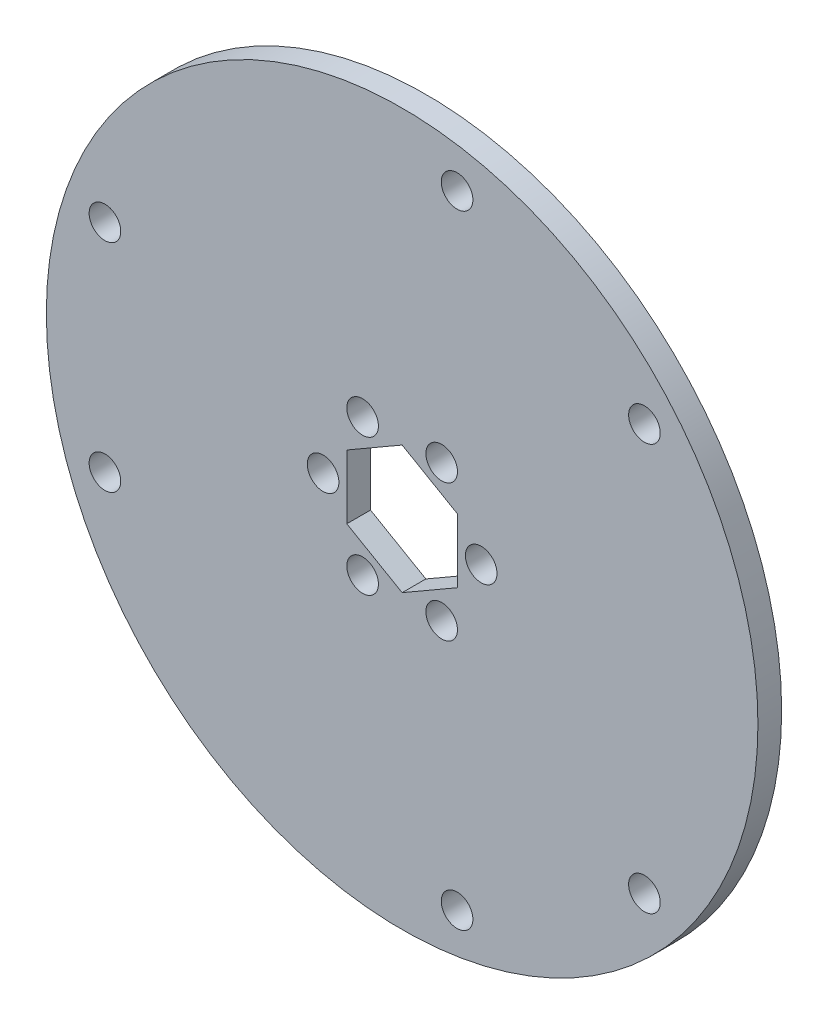
SolidWorks part; units mm, degrees
material "ABS PC"
ref_plane "Front Plane" through (0, 0, 0) normal (0, 0, 1) x (1, 0, 0)
ref_plane "Top Plane" through (0, 0, 0) normal (0, 1, 0) x (1, 0, 0)
ref_plane "Right Plane" through (0, 0, 0) normal (1, 0, 0) x (0, 0, -1)
sketch "Sketch1" plane through (0, 0, 0) normal (0, 0, 1) x (1, 0, 0)
  line L0 (0, 8.0829) -> (7, 4.0415)
  line L1 (-7, -4.0415) -> (-7, 4.0415)
  line L2 (0, -8.0829) -> (-7, -4.0415)
  line L3 (-7, 4.0415) -> (0, 8.0829)
  line L4 (7, -4.0415) -> (0, -8.0829)
  line L5 (7, 4.0415) -> (7, -4.0415)
  circle A0 centre (0, 0) radius 45
  circle A1 centre (-37.5877, 13.6808) radius 2
  circle A2 centre (6.9459, 39.3923) radius 2
  circle A3 centre (30.6418, 25.7115) radius 2
  circle A4 centre (-37.5877, -13.6808) radius 2
  circle A5 centre (6.9459, -39.3923) radius 2
  circle A6 centre (30.6418, -25.7115) radius 2
  circle A7 centre (5, 8.6603) radius 2
  circle A8 centre (-10, 0) radius 2
  circle A9 centre (5, -8.6603) radius 2
  circle A10 centre (-5, 8.6603) radius 2
  circle A11 centre (-5, -8.6603) radius 2
  circle A12 centre (10, 0) radius 2
extrude "Boss-Extrude1" add sketch "Sketch1" along normal blind 3
